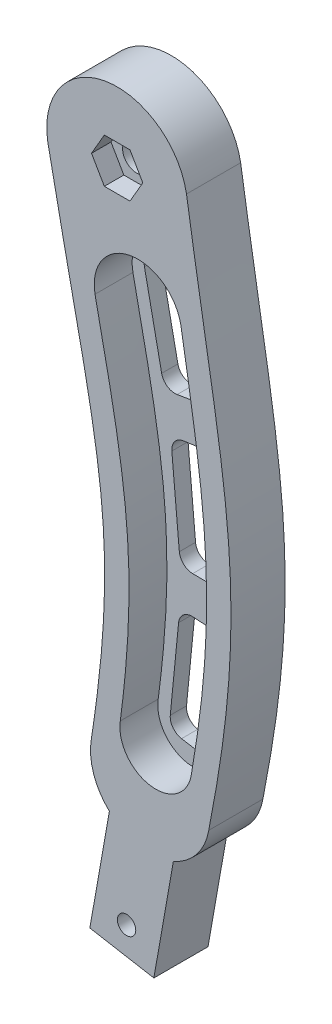
SolidWorks part; units mm, degrees
ref_plane "Front Plane" through (0, 0, 0) normal (0, 0, 1) x (1, 0, 0)
ref_plane "Top Plane" through (0, 0, 0) normal (0, 1, 0) x (1, 0, 0)
ref_plane "Right Plane" through (0, 0, 0) normal (1, 0, 0) x (0, 0, -1)
ref_plane "Plane1" through (0, 0, 348) normal (0, 0, 1) x (1, 0, 0)
sketch "Sketch1" plane through (0, 0, 348) normal (0, 0, 1) x (1, 0, 0)
  line L0 (298.0373, 149.7417) -> (301.2158, 134.2889)
  line L1 (304.0751, 132.3266) -> (309.5338, 133.2354)
  line L2 (311.5907, 136.1031) -> (309.0358, 151.7995)
  line L3 (306.1029, 153.8541) -> (300.0206, 152.7017)
  line L4 (303.0951, 122.8026) -> (304.4782, 107.4006)
  line L5 (306.942, 105.1243) -> (311.3081, 105.0786)
  line L6 (313.8314, 107.698) -> (313.0595, 123.8301)
  line L7 (310.2218, 126.1873) -> (305.2445, 125.5029)
  line L8 (304.3418, 95.9829) -> (302.8073, 80.4197)
  line L9 (304.8846, 77.7083) -> (308.0619, 77.1792)
  line L10 (310.9483, 79.2977) -> (313.1735, 95.1521)
  line L11 (310.8514, 97.9949) -> (306.9833, 98.2329)
  arc A0 (295.2448, 76.3784) -> (316.9106, 72.5581) centre (306.0777, 74.4683) ccw
  arc A1 (312.8025, 172.2574) -> (287.1975, 167.7426) centre (300, 170) ccw
  circle A2 centre (300, 170) radius 2.6
  arc A3 (300.0206, 152.7017) -> (298.0373, 149.7417) centre (300.486, 150.2454) ccw
  arc A4 (301.2158, 134.2889) -> (304.0751, 132.3266) centre (303.6645, 134.7926) ccw
  arc A5 (309.5338, 133.2354) -> (311.5907, 136.1031) centre (309.1232, 135.7015) ccw
  arc A6 (309.0358, 151.7995) -> (306.1029, 153.8541) centre (306.5683, 151.3978) ccw
  arc A7 (305.2445, 125.5029) -> (303.0951, 122.8026) centre (305.585, 123.0262) ccw
  arc A8 (304.4782, 107.4006) -> (306.942, 105.1243) centre (306.9682, 107.6242) ccw
  arc A9 (311.3081, 105.0786) -> (313.8314, 107.698) centre (311.3342, 107.5785) ccw
  arc A10 (313.0595, 123.8301) -> (310.2218, 126.1873) centre (310.5623, 123.7106) ccw
  arc A11 (306.9833, 98.2329) -> (304.3418, 95.9829) centre (306.8297, 95.7376) ccw
  arc A12 (302.8073, 80.4197) -> (304.8846, 77.7083) centre (305.2953, 80.1744) ccw
  arc A13 (308.0619, 77.1792) -> (310.9483, 79.2977) centre (308.4726, 79.6452) ccw
  arc A14 (313.1735, 95.1521) -> (310.8514, 97.9949) centre (310.6978, 95.4996) ccw
  spline S0 degree 3 poles (287.1975, 167.7426) (288.2452, 162.4288) (289.8858, 154.4985) (292.1183, 143.9883) (293.7427, 136.2354) (295.2339, 128.616) (296.4735, 121.1373) (297.3368, 113.7624) (297.7383, 106.4191) (297.6688, 99.0338) (297.0148, 88.9877) (296.0224, 81.4352) (295.2448, 76.3784) knots 0 0 0 0 0.175721 0.262737 0.348607 0.432723 0.514619 0.594501 0.673507 0.753057 0.833978 1 1 1 1
  spline S1 degree 3 poles (316.9106, 72.5581) (317.9931, 78.0601) (319.4367, 86.4195) (320.6441, 97.7467) (321.086, 106.4461) (320.9745, 115.1886) (320.3312, 123.8347) (319.2942, 132.2819) (318.0373, 140.5118) (316.6955, 148.5681) (314.9066, 159.1245) (313.6129, 167.0098) (312.8025, 172.2574) knots 0 0 0 0 0.167265 0.252809 0.339605 0.4269 0.513395 0.598049 0.680669 0.76168 0.841637 1 1 1 1
extrude "Boss-Extrude1" add sketch "Sketch1" along normal blind 10
sketch "Sketch2" plane through (0, 0, 348) normal (0, 0, 1) x (1, 0, 0)
  line L0 (294.9594, 45.9659) -> (306.7771, 43.8821)
  line L1 (306.7771, 43.8821) -> (311.4656, 70.472)
  line L2 (311.4656, 70.472) -> (299.6479, 72.5557)
  line L3 (299.6479, 72.5557) -> (294.9594, 45.9659)
  circle A0 centre (301.7365, 49.8481) radius 1.7
extrude "Boss-Extrude2" add sketch "Sketch2" along normal blind 10
ref_plane "Plane2" through (0, 0, 354.4) normal (0, 0, 1) x (1, 0, 0)
sketch "Sketch3" plane through (0, 0, 354.4) normal (0, 0, 1) x (1, 0, 0)
  line L0 (304.7343, 170) -> (302.3671, 174.1)
  line L1 (302.3671, 174.1) -> (297.6329, 174.1)
  line L2 (297.6329, 174.1) -> (295.2657, 170)
  line L3 (295.2657, 170) -> (297.6329, 165.9)
  line L4 (297.6329, 165.9) -> (302.3671, 165.9)
  line L5 (302.3671, 165.9) -> (304.7343, 170)
extrude "Cut-Extrude1" cut sketch "Sketch3" along normal blind 3.61
ref_plane "Plane3" through (0, 0, 351) normal (0, 0, 1) x (1, 0, 0)
sketch "Sketch4" plane through (0, 0, 351) normal (0, 0, 1) x (1, 0, 0)
  arc A0 (300.5809, 81.8889) -> (313.6964, 79.8733) centre (307.1386, 80.8811) ccw
  arc A1 (311.7546, 150.7923) -> (295.9112, 147.7816) centre (303.8329, 149.2869) ccw
  spline S0 degree 3 poles (295.9112, 147.7816) (296.6977, 144.0585) (297.8781, 138.4988) (299.331, 131.0993) (300.305, 125.6146) (301.1199, 120.1656) (301.7301, 114.7393) (302.1035, 109.3176) (302.2284, 103.8829) (302.1142, 98.4231) (301.6728, 91.0755) (301.0656, 85.5652) (300.5809, 81.8889) knots 0 0 0 0 0.17166 0.256391 0.340163 0.422938 0.504895 0.586427 0.668014 0.750043 0.83271 1 1 1 1
  spline S1 degree 3 poles (313.6964, 79.8733) (314.3753, 83.768) (315.2699, 89.6556) (316.0761, 97.5812) (316.452, 103.6045) (316.5642, 109.6639) (316.3997, 115.7237) (315.9759, 121.7443) (315.3382, 127.6956) (314.5459, 133.5659) (313.3646, 141.2601) (312.395, 146.9887) (311.7546, 150.7923) knots 0 0 0 0 0.166089 0.250039 0.334584 0.419537 0.504541 0.589152 0.673005 0.755934 0.837971 1 1 1 1
extrude "Cut-Extrude2" cut sketch "Sketch4" along normal blind 7.01
ref_plane "Plane4" through (300, 0, 0) normal (1, 0, 0) x (0, 0, -1)
ref_plane "Plane5" through (0, 170, 0) normal (0, 1, 0) x (1, 0, 0)
ref_axis "KNEE_AXIS" through (300, 170, 358.5) along (0, 0, -1)
ref_plane "Plane6" through (301.7365, 0, 0) normal (1, 0, 0) x (0, 0, -1)
ref_plane "Plane7" through (0, 49.8481, 0) normal (0, 1, 0) x (1, 0, 0)
ref_axis "ANKLE_AXIS" through (301.7365, 49.8481, 358.5) along (0, 0, -1)
